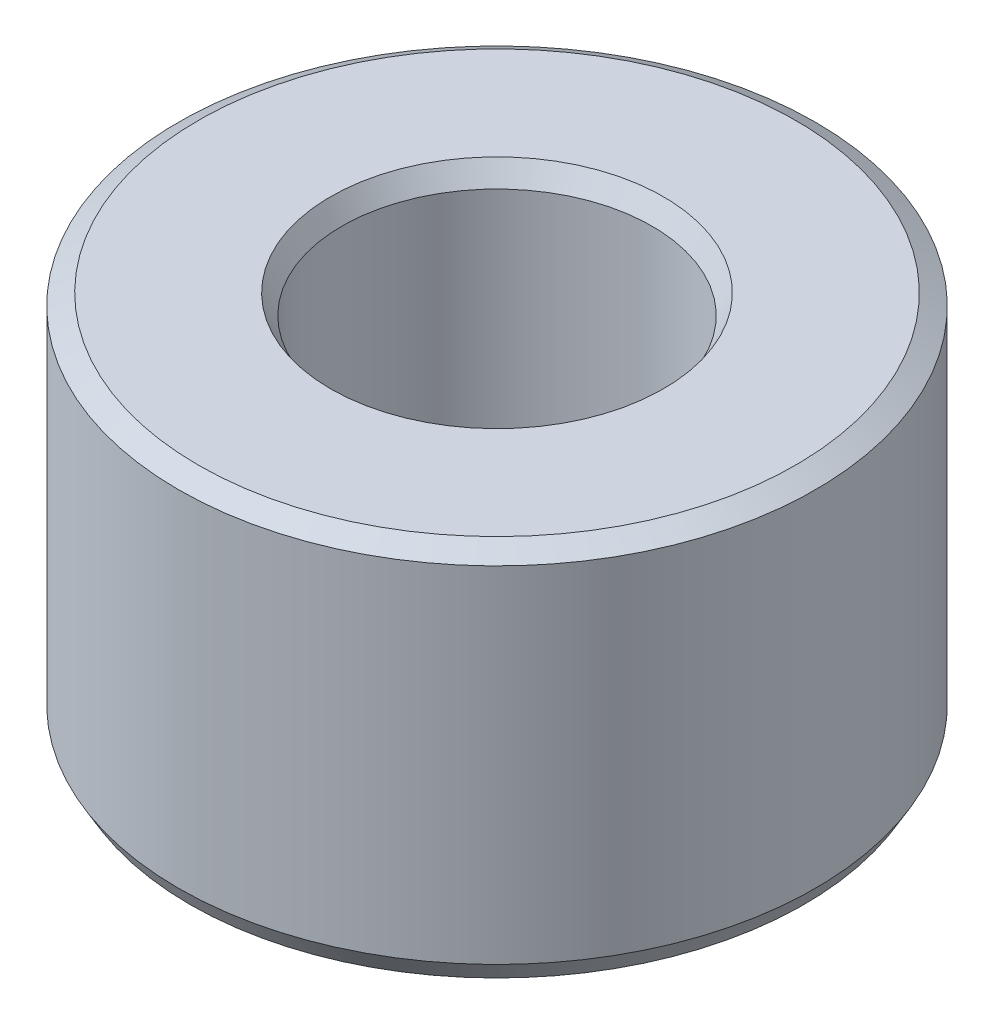
SolidWorks part; units mm, degrees
ref_plane "Front Plane" through (0, 0, 0) normal (0, 0, 1) x (1, 0, 0)
ref_plane "Top Plane" through (0, 0, 0) normal (0, 1, 0) x (1, 0, 0)
ref_plane "Right Plane" through (0, 0, 0) normal (1, 0, 0) x (0, 0, -1)
sketch "Sketch1" plane through (0, 0, 0) normal (0, 1, 0) x (1, 0, 0)
  circle A0 centre (0, 0) radius 37.5
  dimension "SLEEVE_OD" = 75
extrude "Boss-Extrude1" add sketch "Sketch1" along normal blind 44.3257
sketch "Sketch2" plane through (0, 0, 0) normal (0, 1, 0) x (1, 0, 0)
  circle A0 centre (0, 0) radius 18.2595
  dimension "BORE_D" = 36.519
extrude "Cut-Extrude1" cut sketch "Sketch2" along normal through all
chamfer "Chamfer1" distance 1.3448 angle 60 4 edges at (0, 44.3257, 18.2595) (0, 0, 18.2595) (0, 0, 37.5) (0, 44.3257, 37.5) first distance on face at (0, 44.3257, 18.2595) first distance on face at (0, 0, 18.2595) first distance on face at (0, 44.3257, 37.5)
